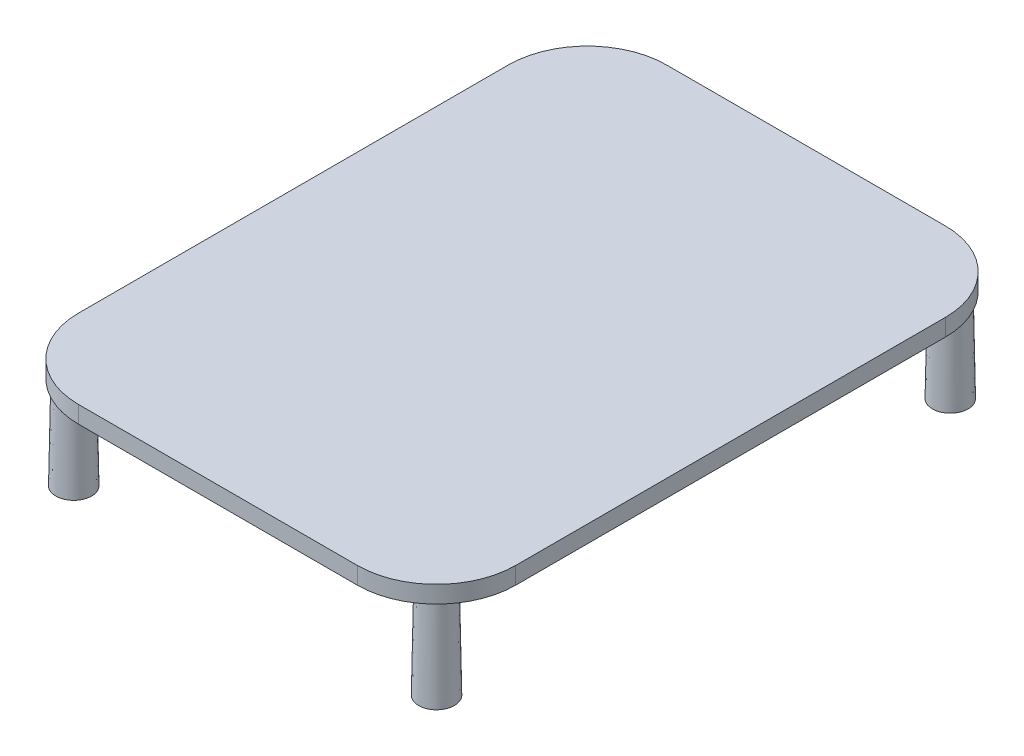
SolidWorks part; units mm, degrees
ref_plane "Front Plane" through (0, 0, 0) normal (0, 0, 1) x (1, 0, 0)
ref_plane "Top Plane" through (0, 0, 0) normal (0, 1, 0) x (1, 0, 0)
ref_plane "Right Plane" through (0, 0, 0) normal (1, 0, 0) x (0, 0, -1)
sketch "Sketch1" plane through (0, 0, 0) normal (0, 1, 0) x (1, 0, 0)
  line L1 (12, 22.5) -> (-12, 22.5)
  line L2 (16, 18.5) -> (16, -18.5)
  line L3 (12, -22.5) -> (-12, -22.5)
  line L4 (-16, 18.5) -> (-16, -18.5)
  line L5 (16, 22.5) -> (-16, -22.5) construction
  line L6 (16, -22.5) -> (-16, 22.5) construction
  arc A0 (-12, 22.5) -> (-16, 18.5) centre (-12, 18.5) ccw
  arc A1 (16, -18.5) -> (12, -22.5) centre (12, -18.5) cw
  arc A2 (12, 22.5) -> (16, 18.5) centre (12, 18.5) cw
  arc A3 (-12, -22.5) -> (-16, -18.5) centre (-12, -18.5) cw
  point P0 (0, 0)
  dimension "D3" = 4
  dimension "D1" = 32
  dimension "D2" = 45
extrude "Boss-Extrude1" add sketch "Sketch1" along normal mid plane 17
sketch "Sketch2" plane through (0, 0, 0) normal (1, 0, 0) x (0, 0, -1)
  line L1 (22.5, 8.5) -> (22.5, -8.5)
  arc A0 (22.5, 8.5) -> (22.5, -8.5) centre (19.8618, 0) cw
  dimension "D1" = 8.9
sketch "Sketch3" plane through (0, 0, 0) normal (0, 1, 0) x (1, 0, 0)
  line L1 (12, 22.5) -> (-12, 22.5)
  line L2 (16, 18.5) -> (16, -18.5)
  line L3 (12, -22.5) -> (-12, -22.5)
  line L4 (-16, 18.5) -> (-16, -18.5)
  line L5 (16, 22.5) -> (-16, -22.5) construction
  line L6 (16, -22.5) -> (-16, 22.5) construction
  arc A0 (-12, 22.5) -> (-16, 18.5) centre (-12, 18.5) ccw
  arc A1 (16, -18.5) -> (12, -22.5) centre (12, -18.5) cw
  arc A2 (12, 22.5) -> (16, 18.5) centre (12, 18.5) cw
  arc A3 (-12, -22.5) -> (-16, -18.5) centre (-12, -18.5) cw
  point P0 (0, 0)
  dimension "D3" = 4
  dimension "D1" = 32
  dimension "D2" = 45
sweep "Sweep1" add profiles "Sketch2" path "Sketch3"
fillet "Fillet1" radius 7 18 edges at (14.8284, -8.5, 21.3284) (0, -8.5, 22.5) (-14.8284, -8.5, 21.3284) (-16, -8.5, 0) (-14.8284, -8.5, -21.3284) (-6, -8.5, -22.5) (6, -8.5, -22.5) (14.8284, -8.5, -21.3284) (14.8284, 8.5, 21.3284) (0, 8.5, 22.5) (-14.8284, 8.5, 21.3284) (-16, 8.5, 0) (-14.8284, 8.5, -21.3284) (-6, 8.5, -22.5) (6, 8.5, -22.5) (14.8284, 8.5, -21.3284) (16, -8.5, 0) (16, 8.5, 0)
sketch "Sketch4" plane through (0, 0, 0) normal (0, 0, 1) x (1, 0, 0)
  line L0 (-18.8245, 7.0263) -> (23.2084, 7.0263)
  line L1 (23.2084, 7.0263) -> (23.2084, -10.9631)
  line L2 (23.2084, -10.9631) -> (-23.5289, -10.9631)
  line L3 (-23.5289, -10.9631) -> (-23.5289, 7.0263)
  line L4 (-23.5289, 7.0263) -> (-18.8245, 7.0263)
extrude "Cut-Extrude1" cut sketch "Sketch4" against normal through all and the other way through all
sketch "Sketch7" plane through (0, 7.0263, 0) normal (0, -1, 0) x (1, 0, 0)
  line L0 (12, 25.3245) -> (-12, 25.3245) construction
  line L1 (-18.8245, 18.5) -> (-18.8245, -18.5) construction
  line L2 (18.8245, -18.5) -> (18.8245, 18.5) construction
  line L3 (0, -25.3245) -> (12, -25.3245) construction
  line L4 (-12, -25.3245) -> (0, -25.3245) construction
  circle A0 centre (-15.6245, 22.1245) radius 1.4
  circle A1 centre (15.6245, 22.1245) radius 1.4
  circle A2 centre (15.6245, -22.1245) radius 1.4
  circle A3 centre (-15.6245, -22.1245) radius 1.4
  dimension "D1" = 2.8
  dimension "D2" = 2.8
  dimension "D3" = 2.8
  dimension "D4" = 2.8
  dimension "D5" = 3.2
  dimension "D6" = 3.2
  dimension "D7" = 3.2
  dimension "D8" = 3.2
  dimension "D9" = 3.2
  dimension "D10" = 3.2
  dimension "D11" = 3.2
  dimension "D12" = 3.2
sketch "Sketch6" plane through (0, 7.0263, 0) normal (0, -1, 0) x (1, 0, 0)
  line L1 (13, 20) -> (-13, 20)
  line L2 (17, 16) -> (17, -16)
  line L3 (13, -20) -> (-13, -20)
  line L4 (-17, 16) -> (-17, -16)
  line L5 (17, 20) -> (-17, -20) construction
  line L6 (17, -20) -> (-17, 20) construction
  arc A0 (-13, 20) -> (-17, 16) centre (-13, 16) ccw
  arc A1 (17, -16) -> (13, -20) centre (13, -16) cw
  arc A2 (13, 20) -> (17, 16) centre (13, 16) cw
  arc A3 (-13, -20) -> (-17, -16) centre (-13, -16) cw
  point P0 (0, 0)
  dimension "D3" = 4
  dimension "D1" = 34
  dimension "D2" = 40
extrude "Cut-Extrude2" cut sketch "Sketch6" against normal blind 0.5
fillet "Fillet2" radius 1 8 edges at (0, 7.5263, 20) (15.8284, 7.5263, 18.8284) (17, 7.5263, 0) (15.8284, 7.5263, -18.8284) (0, 7.5263, -20) (-15.8284, 7.5263, -18.8284) (-17, 7.5263, 0) (-15.8284, 7.5263, 18.8284)
extrude "Boss-Extrude2" add sketch "Sketch7" along normal blind 8 draft 1 draft outward yes
sketch "Sketch11" plane through (0, 0, 0) normal (0, 1, 0) x (1, 0, 0)
  line L1 (12.005, 25.325) -> (-12.005, 25.325)
  line L2 (18.825, 18.505) -> (18.825, -18.505)
  line L3 (12.005, -25.325) -> (-12.005, -25.325)
  line L4 (-18.825, 18.505) -> (-18.825, -18.505)
  line L5 (18.825, 25.325) -> (-18.825, -25.325) construction
  line L6 (18.825, -25.325) -> (-18.825, 25.325) construction
  arc A0 (-12.005, 25.325) -> (-18.825, 18.505) centre (-12.005, 18.505) ccw
  arc A1 (18.825, -18.505) -> (12.005, -25.325) centre (12.005, -18.505) cw
  arc A2 (12.005, 25.325) -> (18.825, 18.505) centre (12.005, 18.505) cw
  arc A3 (-12.005, -25.325) -> (-18.825, -18.505) centre (-12.005, -18.505) cw
  point P0 (0, 0)
  dimension "D3" = 6.82
  dimension "D1" = 37.65
  dimension "D2" = 50.65
extrude "Boss-Extrude4" add sketch "Sketch11" against normal up to vertex (-7.0263 mm away) from surface up to point (0, 7.0263, -25.3245) starting at face at (0, 8.5, -2.3364)
sketch "Sketch12" plane through (0, 0, 0) normal (0, 1, 0) x (1, 0, 0)
  line L1 (17, 20) -> (-17, 20)
  line L2 (17, 20) -> (17, -20)
  line L3 (17, -20) -> (-17, -20)
  line L4 (-17, 20) -> (-17, -20)
  line L5 (17, 20) -> (-17, -20) construction
  line L6 (17, -20) -> (-17, 20) construction
  point P0 (0, 0)
  dimension "D1" = 34
  dimension "D2" = 40
extrude "Cut-Extrude3" cut sketch "Sketch12" along normal blind 0.5 from surface starting at face at (-15.6245, 7.0263, -20.7245)
